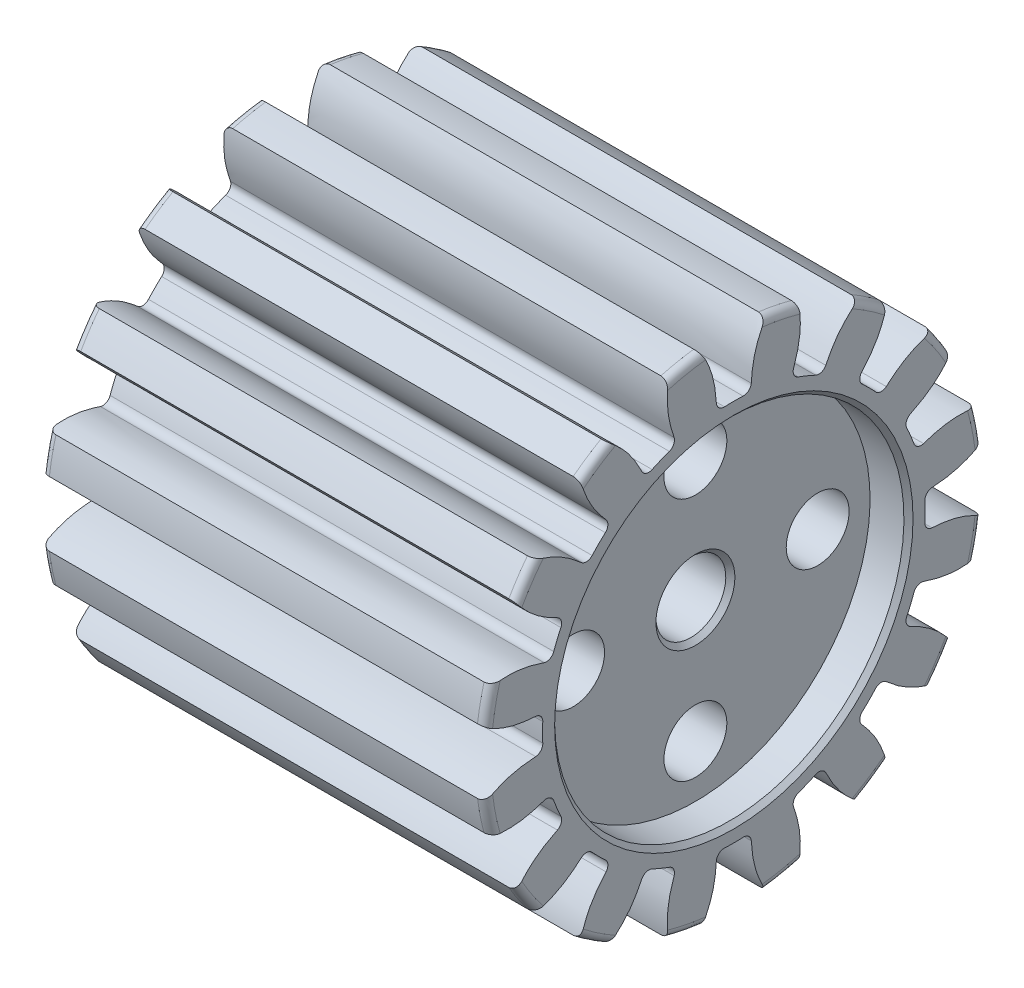
SolidWorks part; units mm, degrees
ref_plane "Front" through (0, 0, 0) normal (0, 0, 1) x (1, 0, 0)
ref_plane "Top" through (0, 0, 0) normal (0, 1, 0) x (1, 0, 0)
ref_plane "Right" through (0, 0, 0) normal (1, 0, 0) x (0, 0, -1)
sketch "Sketch1" plane through (0, 0, 0) normal (0, 0, 1) x (1, 0, 0)
  line L0 (-25.4, 0) -> (25.4, 0) construction
  line L1 (-25.4, 14.351) -> (0, 14.351)
  line L2 (-25.4, 14.351) -> (-25.4, 2)
  line L3 (-25.4, 2) -> (0, 2)
  line L8 (0, 14.351) -> (0, 2)
  dimension "OD" = 28.702
  dimension "For Shaft Diameter" = 4
  dimension "D2" = 25.4
sketch "Sketch2" plane through (0, 0, 0) normal (1, 0, 0) x (0, 0, -1)
  circle A0 centre (0, 0) radius 12.7
  circle A1 centre (0, 0) radius 2
  point P3 (8.9803, 8.9803)
  point P5 (11.7333, 4.8601)
  point P7 (0, -12.7)
  point P8 (-4.8601, -11.7333)
  point P9 (12.7, 0)
  point P10 (11.7333, -4.8601)
  point P11 (-8.9803, -8.9803)
  point P12 (-11.7333, -4.8601)
  point P13 (-12.7, 0)
  point P14 (-11.7333, 4.8601)
  point P15 (-8.9803, 8.9803)
  point P16 (-4.8601, 11.7333)
  point P17 (0, 12.7)
  point P18 (4.8601, 11.7333)
  point P19 (8.9803, -8.9803)
  point P20 (4.8601, -11.7333)
  point P26 (0, 0)
  dimension "Number of Teeth" = 16
sketch "Sketch12" plane through (0, 0, 0) normal (0, 0, 1) x (1, 0, 0)
  line L0 (-25.4, 14.351) -> (-25.4, 2) construction
  line L1 (-25.4, 14.351) -> (0, 14.351) construction
  line L5 (-25.4, 2) -> (0, 2) construction
  line L6 (-25.4, 14.351) -> (-25.4, 2)
  line L7 (-25.4, 14.351) -> (0, 14.351)
  line L11 (-25.4, 2) -> (0, 2)
  line L12 (0, 0) -> (25.4, 0) construction
  line L13 (0, 14.351) -> (0, 2) construction
  line L14 (0, 14.351) -> (0, 2)
revolve "Revolve3" add sketch "Sketch12" angle 360 about L12 region at (-12.7, 8.1755, 0)
sketch "Sketch6" plane through (-25.4, 0, 0) normal (-1, 0, 0) x (0, 0, -1)
  line L0 (-11.7799, 1.0374) -> (-12.651, 1.1141) construction
  line L1 (0, 0) -> (-10.9511, 0) construction
  line L2 (-12.651, 1.1141) -> (-17.3011, 3.2857) construction
  line L3 (0, 0) -> (-14.0752, -2.7997) construction
  line L4 (-17.3011, 3.2857) -> (-17.3011, -3.2857) construction
  line L5 (-17.3011, -3.2857) -> (-12.651, -1.1141) construction
  line L6 (-12.651, -1.1141) -> (-11.7799, -1.0374) construction
  line L7 (-10.9511, 0) -> (-14.351, 0) construction
  line L8 (-10.9089, -0.9607) -> (-10.9089, 0.9607) construction
  line L9 (-10.9089, -0.9607) -> (-11.7799, -1.0374)
  line L10 (-10.9089, 0.9607) -> (-11.7799, 1.0374)
  line L11 (-12.651, -1.1141) -> (-12.651, 1.1141) construction
  line L12 (-10.9089, -0.9607) -> (-12.651, -0.9607) construction
  circle A0 centre (0, 0) radius 12.7 construction
  circle A1 centre (0, 0) radius 10.9511 construction
  arc A2 (-10.9089, 0.9607) -> (-10.9089, -0.9607) centre (0, 0) ccw
  circle A4 centre (0, 0) radius 14.351 construction
  circle A6 centre (0, 0) radius 14.351 construction
  arc A7 (-13.8564, -3.735) -> (-14.231, -1.852) centre (0, 0) cw construction
  arc A8 (-14.231, -1.852) -> (-11.7799, -1.0374) centre (-11.2893, -6.6087) cw
  arc A9 (-11.7799, 1.0374) -> (-14.231, 1.852) centre (-11.2893, 6.6087) cw
  arc A10 (-14.231, 1.852) -> (-14.231, -1.852) centre (0, 0) ccw
  point P1 (-11.7799, -0.9607)
  point P7 (-12.651, 0)
  point P21 (-10.9089, -0.9607)
  point P24 (-10.9089, 0.9607)
  point P32 (-12.651, 0)
  dimension "D4" = 6.35
  dimension "D2" = 11.25
  dimension "D3" = 20
  dimension "D6" = 2.2282
sketch "Sketch7" plane through (0, 0, 0) normal (0, 0, 1) x (1, 0, 0)
  line L0 (-25.4, 0) -> (11.9126, 0)
  line L3 (-25.4, 0) -> (25.4, 0) construction
fillet "Fillet1" radius 0.4445 2 edges at (-25.4, -14.351, 0) (0, -14.351, 0)
sweep "Cut-Sweep1" cut profiles "Sketch6" path "Sketch7" parameters "D1"=0
fillet "Fillet2" radius 0.4456 2 edges
pattern_circular "CirPattern4" count 16 over 360 about axis through (-25.4, 0, 0) along (1, 0, 0) of "Cut-Sweep1", "Fillet2"
sketch "Sketch13" plane through (0, 0, 0) normal (1, 0, 0) x (0, 0, -1)
  circle A0 centre (0, 0) radius 10
  circle A1 centre (0, 7) radius 1.5
  circle A2 centre (7, 0) radius 1.5
  circle A3 centre (0, -7) radius 1.5
  circle A4 centre (-7, 0) radius 1.5
  point P14 (0, 0)
  dimension "D1" = 20
  dimension "D3" = 3
  dimension "D2" = 7
  dimension "D4" = 4
extrude "Cut-Extrude1" cut sketch "Sketch13" against normal blind 2.2 contours A0
chamfer "Chamfer1" distance 0.26 angle 45 3 edges at (-25.4, -2, 0) (0, 10, 0) (-2.2, 2, 0)
hole_wizard "CBORE for M3 SHCS1" positions "Sketch14" profile "Sketch15" counterbore size "M3" standard "ANSI Metric" end condition through all
sketch "Sketch14" plane through (-25.4, 0, 0) normal (-1, 0, 0) x (0, 0, 1)
  point P0 (0, 7)
  point P3 (7, 0)
  point P6 (0, -7)
  point P9 (-7, 0)
sketch "Sketch15" plane through (-25.4, 7, 0) normal (0, 1, 0) x (0, 0, 1)
  line L0 (0, 0) -> (0, 25.4306)
  line L1 (0, 25.4306) -> (1.8, 25.4306)
  line L3 (1.8, 25.4306) -> (1.8, 13.16)
  line L4 (1.8, 13.16) -> (3.25, 13.16)
  line L5 (3.25, 13.16) -> (3.25, 0)
  line L7 (3.25, 0) -> (0, 0)
  line L11 (0, -6.35) -> (0, 107.95) construction
  dimension "Thru Hole Dia." = 3.6
  dimension "Thru Hole Depth" = 25.4306
  dimension "C'Bore Dia." = 6.5
  dimension "C'Bore Depth" = 13.16
equation "\"D1@CirPattern4\" = \"Number of Teeth@Sketch2\""
equation "\"D1@Sketch2\" = \"For Shaft Diameter@Sketch1\""
equation "\"D2@Sketch6\" = 360 / \"Number of Teeth@Sketch2\" / 2"
equation "\"D1@Chamfer1\"=\"For Shaft Diameter@Sketch1\" * 0.065"
